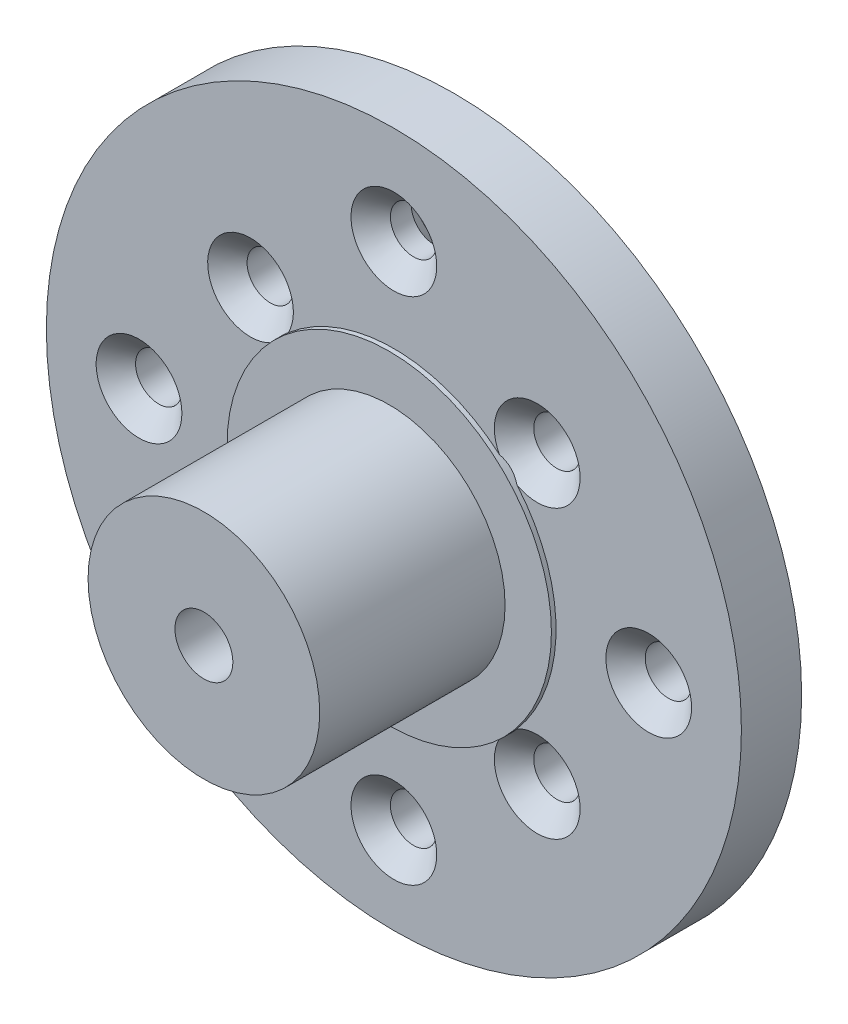
SolidWorks part; units mm, degrees
ref_plane "前视基准面" through (0, 0, 0) normal (0, 0, 1) x (1, 0, 0)
ref_plane "上视基准面" through (0, 0, 0) normal (0, 1, 0) x (1, 0, 0)
ref_plane "右视基准面" through (0, 0, 0) normal (1, 0, 0) x (0, 0, -1)
sketch "草图1" plane through (0, 0, 0) normal (0, 0, 1) x (1, 0, 0)
  circle A0 centre (0, 22) radius 2
  circle A1 centre (-12.3744, 12.3744) radius 2
  arc A3 (-14.4744, 12.3744) -> (-10.2744, 12.3744) centre (-12.3744, 12.3744) ccw construction
  arc A4 (-2.1, 22) -> (2.1, 22) centre (0, 22) ccw construction
  circle A5 centre (22, 0) radius 2
  circle A6 centre (12.3744, 12.3744) radius 2
  circle A7 centre (0, -22) radius 2
  circle A8 centre (12.3744, -12.3744) radius 2
  circle A9 centre (-22, 0) radius 2
  circle A10 centre (-12.3744, -12.3744) radius 2
  circle A11 centre (0, 0.478) radius 30
  point P27 (0, 0)
  dimension "D1" = 4
  dimension "D2" = 4
  dimension "D3" = 60
extrude "凸台-拉伸1" add sketch "草图1" along normal blind 5.2
sketch "草图2" plane through (0, 0, 5.2) normal (0, 0, 1) x (1, 0, 0)
  circle A0 centre (0, 0) radius 14
  dimension "D1" = 28
extrude "凸台-拉伸2" add sketch "草图2" along normal blind 0.4
sketch "草图3" plane through (0, 0, 5.6) normal (0, 0, 1) x (1, 0, 0)
  circle A0 centre (0, 0) radius 10
  dimension "D1" = 20
extrude "凸台-拉伸3" add sketch "草图3" along normal blind 16
sketch "草图4" plane through (0, 0, 21.6) normal (0, 0, 1) x (1, 0, 0)
  circle A0 centre (0, 0) radius 2.5
  dimension "D1" = 5
extrude "切除-拉伸1" cut sketch "草图4" against normal blind 12 contours A0
chamfer "倒角1" distance 1.7 angle 45 9 edges at (2, 22, 0) (2, 22, 5.2) (14.3744, 12.3744, 5.2) (24, 0, 5.2) (14.3744, -12.3744, 5.2) (2, -22, 5.2) (-10.3744, -12.3744, 5.2) (-20, 0, 5.2) (-10.3744, 12.3744, 5.2)
